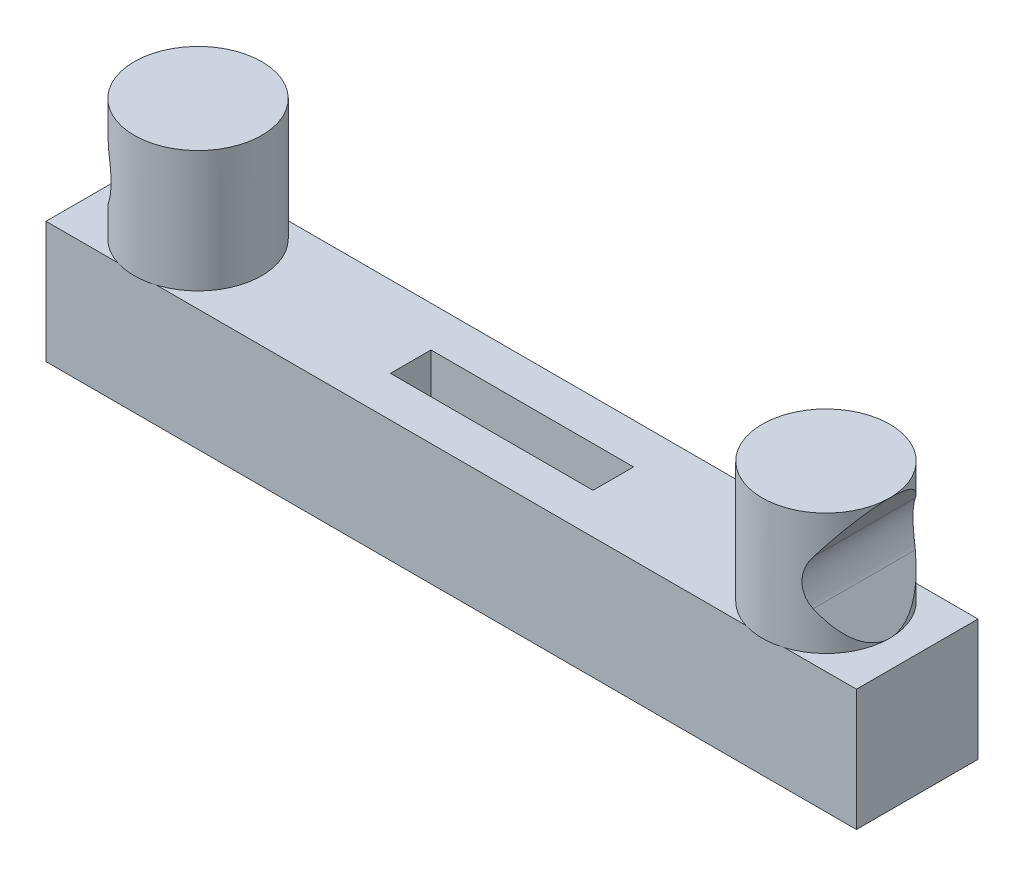
SolidWorks part; units mm, degrees
ref_plane "Front Plane" through (0, 0, 0) normal (0, 0, 1) x (1, 0, 0)
ref_plane "Top Plane" through (0, 0, 0) normal (0, 1, 0) x (1, 0, 0)
ref_plane "Right Plane" through (0, 0, 0) normal (1, 0, 0) x (0, 0, -1)
sketch "Sketch1" plane through (0, 0, 0) normal (0, 1, 0) x (1, 0, 0)
  line L1 (-25.4, 3.81) -> (25.4, 3.81)
  line L2 (-25.4, 3.81) -> (-25.4, -3.81)
  line L3 (-25.4, -3.81) -> (25.4, -3.81)
  line L4 (25.4, 3.81) -> (25.4, -3.81)
  line L5 (-25.4, 3.81) -> (25.4, -3.81) construction
  line L6 (-25.4, -3.81) -> (25.4, 3.81) construction
  point P0 (0, 0)
  dimension "D1" = 7.62
  dimension "D2" = 50.8
extrude "Boss-Extrude1" add sketch "Sketch1" along normal blind 7.62
sketch "Sketch2" plane through (0, 7.62, 0) normal (0, 1, 0) x (1, 0, 0)
  line L1 (-6.35, 1.27) -> (6.35, 1.27)
  line L2 (-6.35, 1.27) -> (-6.35, -1.27)
  line L3 (-6.35, -1.27) -> (6.35, -1.27)
  line L4 (6.35, 1.27) -> (6.35, -1.27)
  line L5 (-6.35, 1.27) -> (6.35, -1.27) construction
  line L6 (-6.35, -1.27) -> (6.35, 1.27) construction
  point P0 (0, 0)
  dimension "D1" = 12.7
  dimension "D2" = 2.54
extrude "Cut-Extrude1" cut sketch "Sketch2" against normal through all
sketch "Sketch3" plane through (0, 7.62, 0) normal (0, 1, 0) x (1, 0, 0)
  circle A0 centre (-19.6812, 0) radius 4
  dimension "D1" = 8
extrude "Boss-Extrude2" add sketch "Sketch3" along normal blind 7.62
sketch "Sketch4" plane through (0, 0, 0) normal (0, 0, 1) x (1, 0, 0)
  line L0 (-23.6812, 15.24) -> (-23.6812, 7.62)
  line L1 (-23.6812, 7.62) -> (-21.1412, 11.43)
  line L2 (-21.1412, 11.43) -> (-23.6812, 15.24)
  dimension "D1" = 2.54
extrude "Cut-Extrude2" cut sketch "Sketch4" against normal blind 7.62 and the other way blind 7.62
fillet "Fillet1" radius 2.54 1 edges at (-21.1412, 11.43, 0)
mirror "Mirror1" about plane through (0, 0, 0) normal (1, 0, 0) of "Boss-Extrude2", "Cut-Extrude2", "Fillet1"
sketch "Sketch5" plane through (0, 15.24, 0) normal (0, 1, 0) x (1, 0, 0)
  circle A0 centre (-19.6812, 0) radius 4 construction
  circle A1 centre (19.6812, 0) radius 4 construction
  circle A2 centre (-19.6812, 0) radius 4
  circle A3 centre (19.6812, 0) radius 4
sketch "Sketch6" plane through (0, 0, 0) normal (0, -1, 0) x (1, 0, 0)
  line L0 (6.35, 1.27) -> (6.35, -1.27) construction
  line L1 (6.35, -1.27) -> (-6.35, -1.27) construction
  line L2 (-6.35, 1.27) -> (6.35, 1.27) construction
  line L3 (-6.35, -1.27) -> (-6.35, 1.27) construction
  line L4 (6.35, 1.27) -> (6.35, -1.27)
  line L5 (6.35, -1.27) -> (-6.35, -1.27)
  line L6 (-6.35, 1.27) -> (6.35, 1.27)
  line L7 (-6.35, -1.27) -> (-6.35, 1.27)
